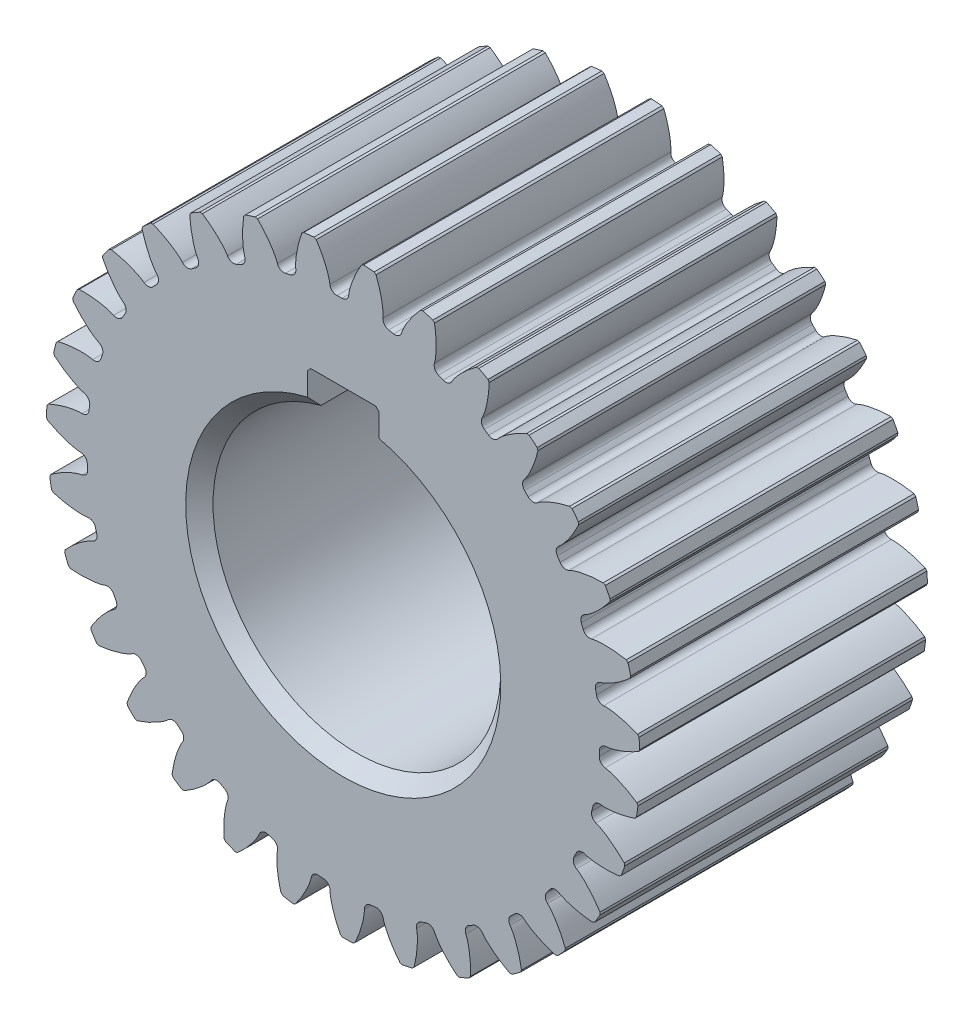
SolidWorks part; units mm, degrees
material "1.6587 (18CrNiMo7-6)"
ref_plane "Front Plane" through (0, 0, 0) normal (0, 0, 1) x (1, 0, 0)
ref_plane "Top Plane" through (0, 0, 0) normal (0, 1, 0) x (1, 0, 0)
ref_plane "Right Plane" through (0, 0, 0) normal (1, 0, 0) x (0, 0, -1)
sketch "Sketch1" plane through (0, 0, 0) normal (0, 0, 1) x (1, 0, 0)
  line L0 (0, 0) -> (0, 25) construction
  line L1 (5, 19.3649) -> (5, 25)
  line L2 (-5, 19.3649) -> (-5, 25)
  line L4 (5, 25) -> (-5, 25)
  line L5 (5, 0) -> (5, 25) construction
  line L6 (-5, 0) -> (-5, 25) construction
  circle A1 centre (0, 0) radius 35.625
  arc A2 (-5, 19.3649) -> (5, 19.3649) centre (0, 0) ccw
  dimension "D1" = 71.25
  dimension "D2" = 40
  dimension "D3" = 25
  dimension "D4" = 5
  dimension "D5" = 5
extrude "Boss-Extrude1" add sketch "Sketch1" along normal blind 40
sketch "Sketch2" plane through (0, 0, 0) normal (0, 0, 1) x (1, 0, 0)
  line L0 (0, 0) -> (38.7457, 0.5775) construction
  line L1 (0, 0) -> (46.061, 3.0248) construction
  arc A0 (35.6131, -0.9194) -> (35.1871, 5.5688) centre (0, 0) ccw
  circle A1 centre (0, 0) radius 38.75 construction
  arc A2 (41.2116, 1.7789) -> (41.0903, 3.6258) centre (0, 0) ccw
  arc A3 (36.4978, 0.0039) -> (35.6131, -0.9194) centre (36.5628, -0.9439) ccw
  arc A4 (36.1849, 4.7691) -> (35.1871, 5.5688) centre (36.1254, 5.7173) cw
  spline S0 degree 4 poles (36.4131, 0) (36.4215, 0.0001) (36.4452, 0.0007) (36.49, 0.003) (36.5629, 0.0086) (36.6558, 0.0182) (36.7758, 0.0336) (36.9169, 0.0555) (37.0718, 0.0835) (37.24, 0.1182) (37.4075, 0.1566) (37.5743, 0.1984) (37.7402, 0.2432) (37.9407, 0.3011) (38.1805, 0.3758) (38.46, 0.4706) (38.7758, 0.587) (39.0964, 0.715) (39.4107, 0.8488) (39.7268, 0.9928) (40.0316, 1.1385) (40.3467, 1.2988) (40.6367, 1.4515) (40.9597, 1.6325) (41.2198, 1.7815) (41.5608, 1.9887) (41.7615, 2.1142) (41.9957, 2.2648) (42.0993, 2.3336) (42.163, 2.3759) knots 0 0 0 0 0 0.005377 0.015084 0.028532 0.04661 0.064855 0.092111 0.119476 0.146842 0.174209 0.201575 0.228941 0.256307 0.307035 0.361767 0.4165 0.471232 0.525964 0.580697 0.635429 0.690161 0.744894 0.799626 0.854358 0.909091 0.954545 1 1 1 1 1 construction
  spline S1 degree 4 poles (36.4978, 0.0039) (36.5497, 0.0074) (36.63, 0.015) (36.7525, 0.03) (36.9169, 0.0555) (37.0718, 0.0835) (37.24, 0.1182) (37.4075, 0.1566) (37.5743, 0.1984) (37.7402, 0.2432) (37.9407, 0.3011) (38.1805, 0.3758) (38.46, 0.4706) (38.7758, 0.587) (39.0964, 0.715) (39.4107, 0.8488) (39.7268, 0.9928) (40.0316, 1.1385) (40.3467, 1.2988) (40.6367, 1.4515) (40.9121, 1.6059) (41.0763, 1.6995) (41.1806, 1.7605) (41.2116, 1.7789) knots 0.013503 0.013503 0.013503 0.013503 0.013503 0.04661 0.064855 0.092111 0.119476 0.146842 0.174209 0.201575 0.228941 0.256307 0.307035 0.361767 0.4165 0.471232 0.525964 0.580697 0.635429 0.690161 0.744894 0.799626 0.822112 0.822112 0.822112 0.822112 0.822112
  spline S2 degree 4 poles (36.1849, 4.7691) (36.2368, 4.7724) (36.3174, 4.7753) (36.4408, 4.7765) (36.6072, 4.7728) (36.7644, 4.7653) (36.9357, 4.7528) (37.1067, 4.7367) (37.2776, 4.7171) (37.4479, 4.6943) (37.6542, 4.6631) (37.9018, 4.6204) (38.1913, 4.563) (38.5196, 4.4889) (38.8542, 4.4039) (39.1832, 4.3124) (39.5155, 4.2109) (39.8367, 4.1064) (40.17, 3.9886) (40.4775, 3.8752) (40.7708, 3.7582) (40.9458, 3.6868) (41.0572, 3.6399) (41.0903, 3.6258) knots 0.013503 0.013503 0.013503 0.013503 0.013503 0.04661 0.064855 0.092111 0.119476 0.146842 0.174209 0.201575 0.228941 0.256307 0.307035 0.361767 0.4165 0.471232 0.525964 0.580697 0.635429 0.690161 0.744894 0.799626 0.822112 0.822112 0.822112 0.822112 0.822112
  dimension "D1" = 71.25
  dimension "D2" = 77.5
  dimension "D3" = 82.5
  dimension "D4" = 1.9
  dimension "D5" = 2.903
extrude "Boss-Extrude2" add sketch "Sketch2" along normal blind 40
chamfer "Chamfer1" distance 0.2 2 edges at (41.2116, 1.7789, 20) (41.0903, 3.6258, 20)
pattern_circular "CirPattern1" count 31 over 360 about axis through (0, 0, 40) along (0, 0, -1) of "Boss-Extrude2", "Chamfer1"
chamfer "Chamfer3" distance 0.5 2 edges at (5, 25, 20) (-5, 25, 20)
chamfer "Chamfer4" distance 1.9 1 edges at (0, -20, 40)
chamfer "Chamfer5" distance 1.5 1 edges at (0, -20, 0)
